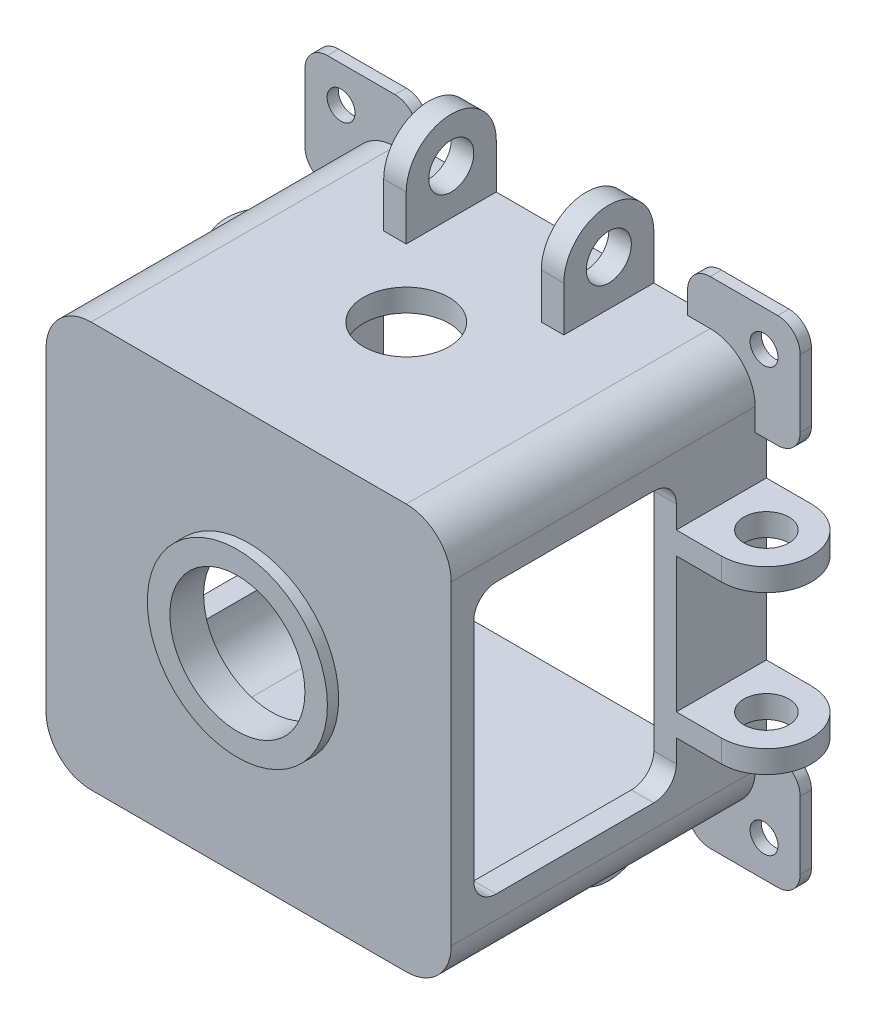
SolidWorks part; units mm, degrees
other "标注1"
sketch "草图6" plane through (67.5, -67.5, 0) normal (0.0299, -0.9992, -0.0283) x (0.0877, 0.0308, -0.9957)
material "2024 合金"
ref_plane "前视基准面" through (0, 0, 0) normal (0, 0, 1) x (1, 0, 0)
ref_plane "上视基准面" through (0, 0, 0) normal (0, 1, 0) x (1, 0, 0)
ref_plane "右视基准面" through (0, 0, 0) normal (1, 0, 0) x (0, 0, -1)
sketch "草图1" plane through (0, 0, 0) normal (0, 0, 1) x (1, 0, 0)
  line L1 (-35, -45) -> (35, -45)
  line L2 (-45, -35) -> (-45, 35)
  line L3 (-35, 45) -> (35, 45)
  line L4 (45, -35) -> (45, 35)
  line L5 (-45, -45) -> (45, 45) construction
  line L6 (-45, 45) -> (45, -45) construction
  line L7 (-30, -40) -> (30, -40)
  line L8 (-40, -30) -> (-40, 30)
  line L9 (-30, 40) -> (30, 40)
  line L10 (40, -30) -> (40, 30)
  line L11 (-40, -40) -> (40, 40) construction
  line L12 (-40, 40) -> (40, -40) construction
  arc A0 (35, -45) -> (45, -35) centre (35, -35) ccw
  arc A1 (30, -40) -> (40, -30) centre (30, -30) ccw
  arc A2 (-35, -45) -> (-45, -35) centre (-35, -35) cw
  arc A3 (-30, -40) -> (-40, -30) centre (-30, -30) cw
  arc A4 (-45, 35) -> (-35, 45) centre (-35, 35) cw
  arc A5 (35, 45) -> (45, 35) centre (35, 35) cw
  arc A6 (30, 40) -> (40, 30) centre (30, 30) cw
  arc A7 (-40, 30) -> (-30, 40) centre (-30, 30) cw
  point P0 (0, 0)
  point P7 (0, 0)
  dimension "D1" = 90
  dimension "D5" = 10
  dimension "D2" = 90
  dimension "D3" = 80
  dimension "D4" = 80
extrude "凸台-拉伸1" add sketch "草图1" along normal blind 70
sketch "草图3" plane through (0, 45, 0) normal (0, 1, 0) x (1, 0, 0)
  line L0 (0, 0) -> (0, -35) construction
  line L1 (35, 0) -> (-35, 0) construction
  circle A0 centre (0, -35) radius 9.5
  dimension "D2" = 19
  dimension "D1" = 35
extrude "切除-拉伸2" cut sketch "草图3" against normal through all
sketch "草图4" plane through (0, -1.9977, 74.2652) normal (1, 0, 0) x (0, 0, -1)
  line L0 (54.2652, -43.0023) -> (54.2652, -53.0023)
  line L1 (74.2652, -53.0023) -> (74.2652, -43.0023)
  line L2 (74.2652, -43.0023) -> (54.2652, -43.0023)
  line L4 (4.2652, -43.0023) -> (74.2652, -43.0023) construction
  arc A0 (54.2652, -53.0023) -> (74.2652, -53.0023) centre (64.2652, -53.0023) ccw
  circle A1 centre (64.2652, -53.0023) radius 5
  dimension "D3" = 10
  dimension "D1" = 20
  dimension "D2" = 10
extrude "凸台-拉伸2" add sketch "草图4" along normal blind 20 and the other way blind 20
sketch "草图5" plane through (0, 0, 0) normal (0, 0, -1) x (-1, 0, 0)
  line L0 (0, 0) -> (0, -60) construction
  line L1 (15, -45) -> (-15, -45)
  line L2 (15, -45) -> (15, -75)
  line L3 (15, -75) -> (-15, -75)
  line L4 (-15, -45) -> (-15, -75)
  line L5 (15, -45) -> (-15, -75) construction
  line L6 (15, -75) -> (-15, -45) construction
  line L7 (45, -45) -> (-45, -45) construction
  point P0 (0, -60)
  dimension "D1" = 30
  dimension "D2" = 30
extrude "切除-拉伸3" cut sketch "草图5" against normal through all
ref_plane "基准面1" through (0, 0, 0) normal (0, -1, 0) x (-1, 0, 0)
ref_plane "基准面2" through (0, 0, 0) normal (1, 0, 0) x (0, 0, -1)
ref_axis "基准轴1" through (0, 0, 63) along (0, 0, -1)
pattern_circular "阵列(圆周)3" count 4 over 360 about axis through (0, 0, 63) along (0, 0, -1) of "切除-拉伸3", "凸台-拉伸2"
sketch "草图13" plane through (0, 0, 70) normal (0, 0, 1) x (1, 0, 0)
  line L1 (40, 40) -> (-40, 40)
  line L2 (40, 40) -> (40, -40)
  line L3 (40, -40) -> (-40, -40)
  line L4 (-40, 40) -> (-40, -40)
  line L5 (40, 40) -> (-40, -40) construction
  line L6 (40, -40) -> (-40, 40) construction
  circle A0 centre (0, 0) radius 15
  point P0 (0, 0)
  dimension "D3" = 30
  dimension "D1" = 80
  dimension "D2" = 80
extrude "凸台-拉伸3" add sketch "草图13" against normal blind 5
sketch "草图14" plane through (0, 0, 70) normal (0, 0, 1) x (1, 0, 0)
  circle A0 centre (0, 0) radius 15
  circle A1 centre (0, 0) radius 20
  dimension "D1" = 30
  dimension "D2" = 40
extrude "凸台-拉伸4" add sketch "草图14" along normal blind 2.5 and the other way blind 7.5
sketch "草图15" plane through (0, 0, 0) normal (0, 0, -1) x (-1, 0, 0)
  line L0 (-50, 50) -> (-30, 30) construction
  line L1 (-40, -30) -> (-40, 30) construction
  line L3 (-30, 40) -> (30, 40) construction
  line L4 (-40, 30) -> (-50, 30)
  line L5 (-30, 40) -> (-30, 50)
  line L6 (-35, 55) -> (-50, 55)
  line L7 (-55, 35) -> (-55, 50)
  arc A0 (-30, 40) -> (-40, 30) centre (-30, 30) ccw construction
  arc A1 (-40, 30) -> (-30, 40) centre (-30, 30) cw
  arc A2 (-50, 55) -> (-55, 50) centre (-50, 50) ccw
  arc A3 (-30, 50) -> (-35, 55) centre (-35, 50) ccw
  arc A4 (-50, 30) -> (-55, 35) centre (-50, 35) cw
  circle A6 centre (-46.9706, 46.9706) radius 3.1
  point P17 (-55, 55)
  point P20 (-30, 55)
  point P23 (-55, 30)
  point P25 (0, 0)
  dimension "D3" = 5
  dimension "D4" = 6.2
  dimension "D1" = 25
  dimension "D2" = 25
  dimension "D5" = 24
extrude "凸台-拉伸5" add sketch "草图15" against normal blind 2.5
mirror "镜向2" about plane through (0, 0, 0) normal (1, 0, 0) of "凸台-拉伸5"
mirror "镜向3" about plane through (0, 0, 0) normal (0, -1, 0) of "镜向2"
sketch "草图16" plane through (-45, 0, 0) normal (-1, 0, 0) x (0, 0, 1)
  line L0 (20, -15) -> (20, -20) construction
  line L1 (25, 30) -> (60, 30)
  line L2 (20, 25) -> (20, -25)
  line L3 (25, -30) -> (60, -30)
  line L4 (65, 25) -> (65, -25)
  line L5 (20, 30) -> (65, -30) construction
  line L6 (20, -30) -> (65, 30) construction
  line L7 (70, 35) -> (70, -35) construction
  line L8 (0, 0) -> (42.5, 0) construction
  arc A0 (60, 30) -> (65, 25) centre (60, 25) cw
  arc A1 (25, 30) -> (20, 25) centre (25, 25) ccw
  arc A2 (20, -25) -> (25, -30) centre (25, -25) ccw
  arc A3 (60, -30) -> (65, -25) centre (60, -25) ccw
  point P0 (42.5, 0)
  dimension "D3" = 5
  dimension "D1" = 5
  dimension "D2" = 60
extrude "切除-拉伸6" cut sketch "草图16" against normal through all
